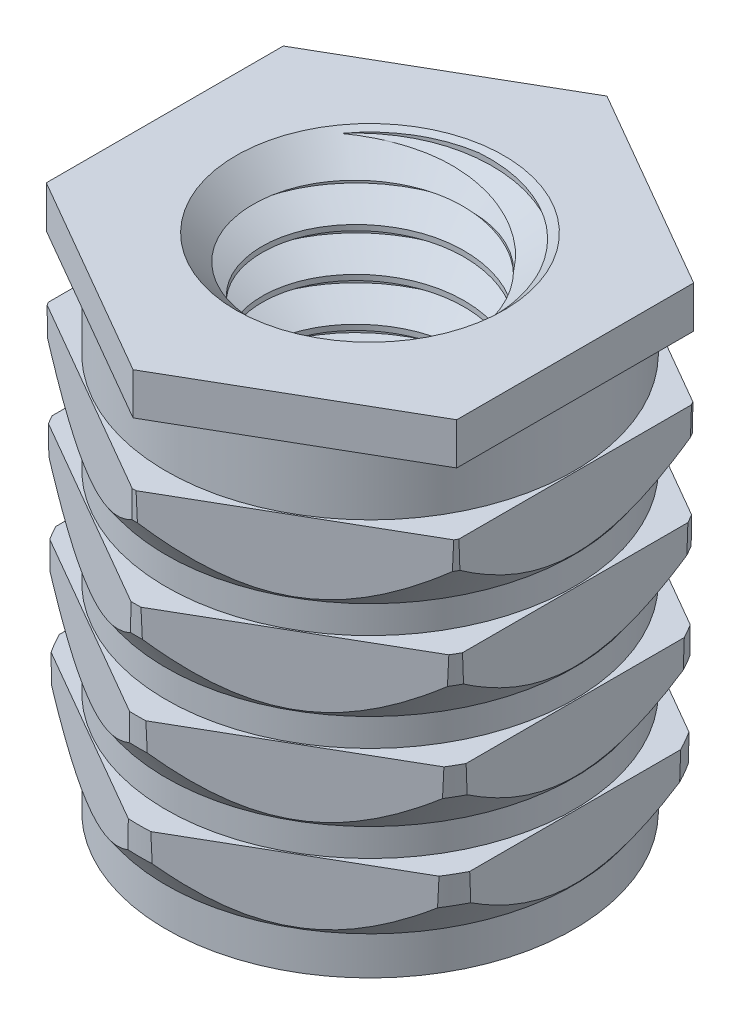
SolidWorks part; units mm, degrees
ref_plane "Front Plane" through (0, 0, 0) normal (0, 0, 1) x (1, 0, 0)
ref_plane "Top Plane" through (0, 0, 0) normal (0, 1, 0) x (1, 0, 0)
ref_plane "Right Plane" through (0, 0, 0) normal (1, 0, 0) x (0, 0, -1)
sketch "Sketch1" plane through (0, 0, 0) normal (0, 1, 0) x (1, 0, 0)
  line L0 (-2.36, 0) -> (2.36, 0) construction
  line L1 (-2.36, 0) -> (-2.375, 0) construction
  line L2 (0, 2.7424) -> (-2.375, 1.3712)
  line L3 (-2.375, 1.3712) -> (-2.375, -1.3712)
  line L4 (-2.375, -1.3712) -> (0, -2.7424)
  line L5 (0, -2.7424) -> (2.375, -1.3712)
  line L6 (2.375, -1.3712) -> (2.375, 1.3712)
  line L7 (2.375, 1.3712) -> (0, 2.7424)
  line L8 (2.36, 0) -> (2.375, 0) construction
  line L9 (-2.7424, 0) -> (-2.375, 0) construction
  circle A0 centre (0, 0) radius 2.36 construction
  circle A1 centre (0, 0) radius 2.375 construction
  circle A2 centre (0, 0) radius 2.7424 construction
  dimension "OD" = 4.72
  dimension "Hex" = 4.75
extrude "Extrude1" add sketch "Sketch1" against normal blind 5.8
sketch "Sketch2" plane through (0, 0, 0) normal (0, 1, 0) x (1, 0, 0)
  circle A2 centre (0, 0) radius 1.5
  point P0 (-1.5, 0)
  dimension "Internal Thread OD" = 3
curve "Helix/Spiral1" pitch 0.5 height 6.8381 radius 1.5 centre (0, 0, 0) axis (0, -1, 0) start towards (0, 0, 1) parameters "Internal Thread Height"=6.8381, "Internal Thread Pitch"=0.5
sketch "Sketch3" plane through (0, 0, 0) normal (0, 0, 1) x (1, 0, 0)
  line L0 (-1.1211, 0.2813) -> (-1.1211, -0.2188) construction
  line L1 (-1.1211, -0.2188) -> (-1.5541, 0.0312) construction
  line L2 (-1.5541, 0.0312) -> (-1.1211, 0.2813) construction
  line L3 (-1.1211, 0.0312) -> (-1.1752, 0.0312) construction
  line L4 (-1.1752, 0.0312) -> (-1.5, 0.0312) construction
  line L5 (-1.5, 0.0312) -> (-1.5541, 0.0312) construction
  line L6 (-1.5, 0.0625) -> (-1.5, 0)
  line L7 (-1.1752, -0.1875) -> (-1.1752, 0.25) construction
  line L11 (-1.5, 0) -> (-1.1482, -0.2031)
  line L12 (-1.1482, -0.2031) -> (-1.1482, 0.2656)
  line L13 (-1.1482, 0.2656) -> (-1.5, 0.0625)
  point P18 (-1.1482, 0.0313)
  dimension "D1" = 0.5
  dimension "D2" = 0.0625
sketch "Sketch4" plane through (0, 0, 0) normal (0, 1, 0) x (-1, 0, 0)
  circle A0 centre (0, 0) radius 1.1752
extrude "Extrude2" cut sketch "Sketch4" against normal through all
chamfer "Chamfer1" distance 0.375 angle 45 2 edges at (0, 0, 1.1752) (0, -5.8, 1.1752)
sweep "Cut-Sweep1" cut profiles "Sketch3" path "Helix/Spiral1" align with end faces yes
sketch "Sketch5" plane through (0, 0, 0) normal (0, 0, 1) x (1, 0, 0)
  line L0 (2.7424, 0) -> (-2.7424, 0) construction
  line L1 (-2.36, 0) -> (-2.36, -5.8) construction
  line L2 (-2.36, 0) -> (-2.7424, 0) construction
  line L3 (0, 0) -> (0, -5.8) construction
  line L4 (-2.375, -5.8) -> (0, -5.8) construction
  line L5 (-2.36, -5.8) -> (-2.7424, -5.8)
  line L6 (-2.7424, 0) -> (-2.375, 0) construction
  line L7 (-2.7424, 0) -> (-2.7424, -5.8) construction
  line L8 (-2.7424, -0.4833) -> (-2.6496, -5.8) construction
  line L9 (-2.7424, -0.4833) -> (-2.36, -0.4833)
  line L10 (-2.7424, 0) -> (-2.7424, -0.4833)
  line L11 (-2.36, -0.4833) -> (-2.36, -1.2083)
  line L12 (-2.6842, -3.8193) -> (-2.36, -4.2823)
  line L13 (-2.36, -5.8) -> (-2.36, -5.3577)
  line L14 (-2.36, -4.2823) -> (-2.36, -4.6023)
  line L15 (-2.36, -1.2083) -> (-2.7298, -1.2083)
  line L16 (-2.7298, -1.2083) -> (-2.7242, -1.5283)
  line L17 (-2.7242, -1.5283) -> (-2.36, -2.0484)
  line L18 (-2.36, -4.6023) -> (-2.6705, -4.6023)
  line L19 (-2.7424, 0) -> (-3.1248, 0)
  line L20 (-3.1248, 0) -> (-3.1248, -5.8)
  line L21 (-3.1248, -5.8) -> (-2.7424, -5.8)
  line L22 (-2.36, -2.3683) -> (-2.7095, -2.3683)
  line L23 (-2.36, -2.0484) -> (-2.36, -2.3683)
  line L24 (-2.7095, -2.3683) -> (-2.7039, -2.6883)
  line L25 (-2.7039, -2.6883) -> (-2.36, -3.1794)
  line L26 (-2.36, -3.4994) -> (-2.6898, -3.4994)
  line L27 (-2.6898, -3.4994) -> (-2.6842, -3.8193)
  line L28 (-2.6705, -4.6023) -> (-2.6649, -4.9222)
  line L29 (-2.36, -3.1794) -> (-2.36, -3.4994)
  line L30 (-2.6649, -4.9222) -> (-2.36, -5.3577)
  dimension "D1" = 0.4833
  dimension "D2" = 1
  dimension "D3" = 1.16
  dimension "D5" = 35
  dimension "D6" = 0.725
revolve "Cut-Revolve1" cut sketch "Sketch5" angle 360 about L3
equation "\"Internal Thread Height@Helix/Spiral1\" = \"Internal Thread Pitch@Helix/Spiral1\" + \"Length@Extrude1\" + 0.5381"
equation "\"D1@Sketch3\" = \"Internal Thread Pitch@Helix/Spiral1\""
equation "\"D2@Sketch3\" = \"D1@Sketch3\" * 1 / 8"
equation "\"D1@Chamfer1\" = \"Internal Thread Pitch@Helix/Spiral1\" * 6 / 8"
equation "\"D1@Sketch5\" = \"Length@Extrude1\"  * 1 / 12"
equation "\"D6@Sketch5\" = \"D1@Sketch5\" * 1.5"
equation "\"D3@Sketch5\" = \"Length@Extrude1\"  * 1 / 5"
